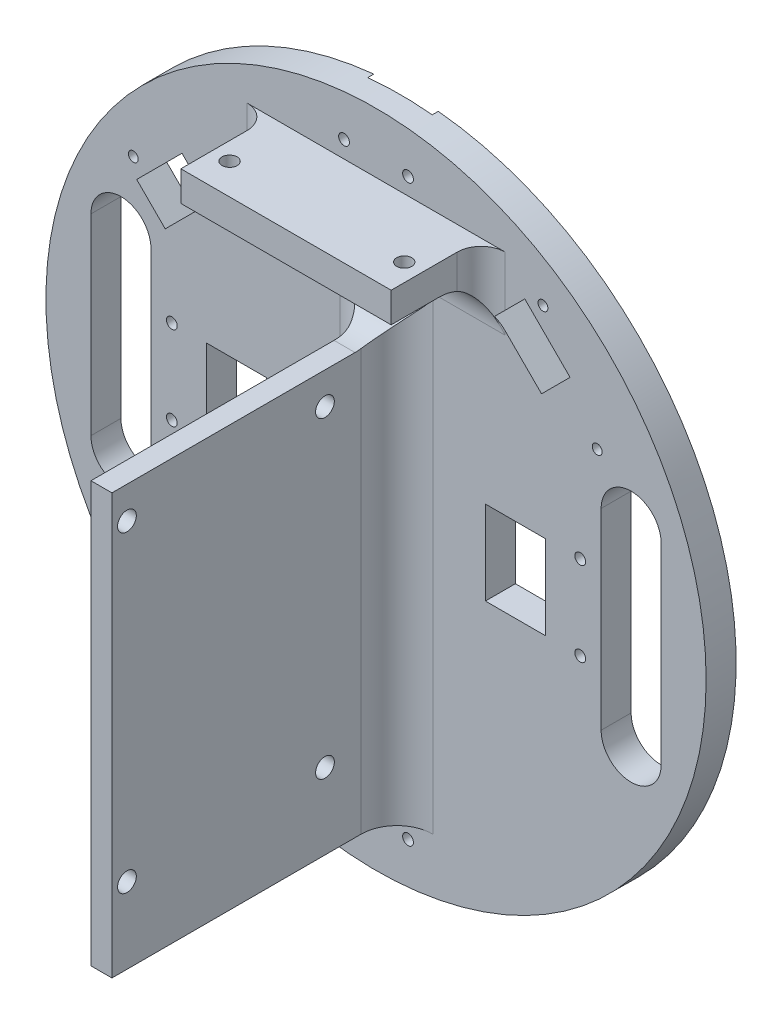
SolidWorks part; units mm, degrees
ref_plane "Front Plane" through (0, 0, 0) normal (0, 0, 1) x (1, 0, 0)
ref_plane "Top Plane" through (0, 0, 0) normal (0, 1, 0) x (1, 0, 0)
ref_plane "Right Plane" through (0, 0, 0) normal (1, 0, 0) x (0, 0, -1)
sketch "Master" plane through (0, 0, 0) normal (0, 0, 1) x (1, 0, 0)
  line L0 (-43.2054, -8.89) -> (-43.2054, 8.89) construction
  line L1 (-46.7961, 27.6322) -> (-27.6322, 46.7961) construction
  line L2 (-69.85, -69.85) -> (69.85, -69.85) construction
  line L3 (-69.85, -69.85) -> (-69.85, 69.85) construction
  line L4 (-69.85, 69.85) -> (69.85, 69.85) construction
  line L5 (69.85, -69.85) -> (69.85, 69.85) construction
  line L6 (-69.85, -69.85) -> (69.85, 69.85) construction
  line L7 (-53.975, 20.32) -> (-53.975, -20.32) construction
  line L8 (-47.625, 20.32) -> (-47.625, -20.32)
  line L9 (-60.325, 20.32) -> (-60.325, -20.32)
  line L10 (0, 69.85) -> (0, -69.85) construction
  line L11 (53.975, 20.32) -> (53.975, -20.32) construction
  line L14 (-18.4785, 50.7873) -> (18.4785, 50.7873) construction
  line L15 (-28.39, -5.09) -> (37.71, -5.09) construction
  line L16 (-28.39, -5.09) -> (-28.39, -46.99) construction
  line L17 (-28.39, -46.99) -> (37.71, -46.99) construction
  line L18 (37.71, -5.09) -> (37.71, -46.99) construction
  line L19 (-14.732, 57.3532) -> (14.732, 57.3532) construction
  line L20 (-14.732, 57.3532) -> (-14.732, 54.5338) construction
  line L21 (-43, 1.27) -> (43, 1.27) construction
  line L22 (-43, 1.27) -> (-43, -53.34) construction
  line L23 (-43, -53.34) -> (43, -53.34) construction
  line L24 (43, 1.27) -> (43, -53.34) construction
  line L25 (-43, 1.27) -> (43, -53.34) construction
  line L26 (-43, -53.34) -> (43, 1.27) construction
  line L27 (-14.732, 44.2468) -> (14.732, 44.2468) construction
  line L28 (14.732, 57.3532) -> (14.732, 54.5338) construction
  line L29 (-14.732, 57.3532) -> (14.732, 44.2468) construction
  line L30 (-14.732, 44.2468) -> (14.732, 57.3532) construction
  line L31 (-18.4785, 54.5338) -> (-14.732, 54.5338) construction
  line L32 (-18.4785, 47.0408) -> (-14.732, 47.0408) construction
  line L33 (14.732, 54.5338) -> (18.4785, 54.5338) construction
  line L34 (14.732, 47.0408) -> (18.4785, 47.0408) construction
  line L35 (-14.732, 47.0408) -> (-14.732, 44.2468) construction
  line L36 (14.732, 47.0408) -> (14.732, 44.2468) construction
  line L37 (-69.85, 69.85) -> (69.85, -69.85) construction
  line L38 (-46.7961, 27.6322) -> (-54.4832, 35.3193) construction
  line L39 (-54.4832, 35.3193) -> (-35.3193, 54.4832) construction
  line L40 (-27.6322, 46.7961) -> (-35.3193, 54.4832) construction
  line L41 (-46.7961, 27.6322) -> (-35.3193, 54.4832) construction
  line L42 (-54.4832, 35.3193) -> (-27.6322, 46.7961) construction
  line L43 (41.0577, 41.0577) -> (31.4758, 50.6397)
  line L44 (41.0577, 41.0577) -> (35.023, 35.023)
  line L45 (31.4758, 50.6397) -> (25.4411, 44.6049)
  line L46 (35.023, 35.023) -> (25.4411, 44.6049)
  line L47 (27.6322, 46.7961) -> (46.7961, 27.6322) construction
  line L48 (27.6322, 46.7961) -> (35.3193, 54.4832) construction
  line L49 (35.3193, 54.4832) -> (54.4832, 35.3193) construction
  line L50 (47.625, 20.32) -> (47.625, -20.32)
  line L51 (-71.8058, -5.08) -> (-14.605, -5.08) construction
  line L52 (-71.8058, -5.08) -> (-71.8058, 5.08) construction
  line L53 (-71.8058, 5.08) -> (-14.605, 5.08) construction
  line L54 (-14.605, -5.08) -> (-14.605, 5.08) construction
  line L55 (-71.8058, -5.08) -> (-14.605, 5.08) construction
  line L56 (-71.8058, 5.08) -> (-14.605, -5.08) construction
  line L57 (60.325, 20.32) -> (60.325, -20.32)
  line L58 (71.8058, 5.08) -> (14.605, 5.08) construction
  line L59 (71.8058, 5.08) -> (14.605, -5.08) construction
  line L60 (14.605, -5.08) -> (14.605, 5.08) construction
  line L61 (71.8058, -5.08) -> (14.605, 5.08) construction
  line L62 (71.8058, -5.08) -> (14.605, -5.08) construction
  line L63 (-41.0577, 41.0577) -> (-50.6397, 31.4758)
  line L64 (-41.0577, 41.0577) -> (-35.023, 35.023)
  line L65 (-50.6397, 31.4758) -> (-44.6049, 25.4411)
  line L66 (-35.023, 35.023) -> (-44.6049, 25.4411)
  line L67 (46.7961, 27.6322) -> (54.4832, 35.3193) construction
  line L68 (27.6322, 46.7961) -> (54.4832, 35.3193) construction
  line L69 (35.3193, 54.4832) -> (46.7961, 27.6322) construction
  line L70 (35.8394, -8.89) -> (23.1394, -8.89)
  line L71 (-35.8394, 8.89) -> (-23.1394, 8.89)
  line L72 (-35.8394, 8.89) -> (-35.8394, -8.89)
  line L73 (-35.8394, -8.89) -> (-23.1394, -8.89)
  line L74 (-23.1394, 8.89) -> (-23.1394, -8.89)
  line L75 (23.1394, 8.89) -> (23.1394, -8.89)
  line L76 (35.8394, 8.89) -> (23.1394, 8.89)
  line L77 (35.8394, 8.89) -> (35.8394, -8.89)
  circle A0 centre (0, 0) radius 69.85
  arc A1 (-47.625, 20.32) -> (-60.325, 20.32) centre (-53.975, 20.32) ccw
  arc A2 (-60.325, -20.32) -> (-47.625, -20.32) centre (-53.975, -20.32) ccw
  circle A3 centre (-43.2054, -8.89) radius 1.143
  circle A4 centre (-43.2054, 8.89) radius 1.143
  arc A7 (47.625, 20.32) -> (60.325, 20.32) centre (53.975, 20.32) cw
  arc A8 (60.325, -20.32) -> (47.625, -20.32) centre (53.975, -20.32) cw
  circle A9 centre (-28.39, -5.09) radius 1.9844 construction
  circle A10 centre (37.71, -5.09) radius 1.9844 construction
  circle A11 centre (37.71, -46.99) radius 1.9844 construction
  circle A12 centre (-28.39, -46.99) radius 1.9844 construction
  arc A13 (-18.4785, 54.5338) -> (-18.4785, 47.0408) centre (-18.4785, 50.7873) ccw construction
  arc A14 (18.4785, 47.0408) -> (18.4785, 54.5338) centre (18.4785, 50.7873) ccw construction
  circle A15 centre (-18.4785, 50.7873) radius 1.6002 construction
  circle A16 centre (18.4785, 50.7873) radius 1.6002 construction
  circle A17 centre (-51.3581, 35.3193) radius 1.0414
  circle A18 centre (-30.7574, 46.7961) radius 1.0414
  circle A19 centre (35.3193, 51.3581) radius 1.0414
  circle A20 centre (46.7961, 30.7574) radius 1.0414
  circle A21 centre (43.2054, -8.89) radius 1.143
  circle A22 centre (43.2054, 8.89) radius 1.143
  point P0 (3.175, -31.115)
  point P3 (-69.85, 0)
  point P4 (69.85, 0)
  point P6 (0, -69.85)
  point P9 (-43.2054, 0)
  point P12 (-53.975, 0)
  point P23 (53.975, 0)
  point P45 (0, -26.035)
  point P48 (0, 50.8)
  point P50 (0, 44.5902)
  point P63 (0, 69.85)
  point P71 (-41.0577, 41.0577)
  point P76 (-49.3914, 49.3914)
  point P77 (-43.2054, 0)
  point P79 (0, -53.34)
  point P85 (41.0577, 41.0577)
  point P91 (49.3914, 49.3914)
  point P109 (0, 0)
  dimension "D1" = 40.64
  dimension "D4" = 2.286
  dimension "D7" = 3.9688
  dimension "D8" = 86
  dimension "D17" = 3.2004
  dimension "D18" = 3.2004
  dimension "D23" = 2.0828
  dimension "D24" = 2.0828
  dimension "D38" = 139.7
  dimension "D2" = 12.7
  dimension "D5" = 66.1
  dimension "D6" = 41.9
  dimension "D9" = 54.61
  dimension "D10" = 14.61
  dimension "D11" = 6.35
  dimension "D12" = 29.464
  dimension "D13" = 36.957
  dimension "D14" = 7.493
  dimension "D15" = 13.1064
  dimension "D16" = 2.8194
  dimension "D19" = 17.78
  dimension "D20" = 19.05
  dimension "D21" = 10.8712
  dimension "D22" = 27.1018
  dimension "D25" = 2.2098
  dimension "D26" = 2.2098
  dimension "D27" = 2.2098
  dimension "D28" = 2.2098
  dimension "D29" = 6.35
  dimension "D31" = 13.97
  dimension "D32" = 9.525
  dimension "D33" = 16.51
  dimension "D34" = 45.72
  dimension "D35" = 10.16
  dimension "D37" = 10.7696
  dimension "D39" = 12.7
  dimension "D36" = 7.366
  dimension "D30" = 2
extrude "Boss-Extrude1" add sketch "Master" along normal blind 6.35 contours A0 A21 A18 A17 A16 A15 A12 A11 A10 A9 A4 A3 A2 L9 A1 L8 L57 A8 L50 A7 A22 region at (0.0831, -0.7021, 0)
sketch "Sketch23" plane through (0, 0, 0) normal (0, 0, 1) x (1, 0, 0)
  line L1 (-22.25, 57.15) -> (22.25, 57.15)
  line L2 (-22.25, 57.15) -> (-22.25, 50.8)
  line L3 (-22.25, 50.8) -> (22.25, 50.8)
  line L4 (22.25, 57.15) -> (22.25, 50.8)
  line L6 (0, 69.85) -> (0, -69.85) construction
  point P4 (0, 57.15)
  dimension "D1" = 44.5
  dimension "D2" = 6.35
  dimension "D3" = 12.7
extrude "Boss-Extrude5" add sketch "Sketch23" along normal blind 25.4
sketch "Sketch11" plane through (0, 0, 0) normal (0, 0, 1) x (1, 0, 0)
  line L0 (6.7691, 60.7441) -> (-6.7691, 60.7441) construction
  line L1 (6.7691, 57.9882) -> (-6.7691, 57.9882)
  line L2 (6.7691, 63.5) -> (-6.7691, 63.5)
  line L3 (0, 0) -> (-27.6628, 0) construction
  line L4 (0, 69.85) -> (0, -69.85) construction
  line L5 (6.7691, -60.7441) -> (-6.7691, -60.7441) construction
  line L6 (6.7691, -57.9882) -> (-6.7691, -57.9882)
  line L7 (6.7691, -63.5) -> (-6.7691, -63.5)
  arc A0 (6.7691, 57.9882) -> (6.7691, 63.5) centre (6.7691, 60.7441) ccw
  arc A1 (-6.7691, 63.5) -> (-6.7691, 57.9882) centre (-6.7691, 60.7441) ccw
  circle A2 centre (-6.7691, 60.7441) radius 1.143
  circle A3 centre (6.7691, 60.7441) radius 1.143
  arc A4 (6.7691, -57.9882) -> (6.7691, -63.5) centre (6.7691, -60.7441) cw
  arc A5 (-6.7691, -63.5) -> (-6.7691, -57.9882) centre (-6.7691, -60.7441) cw
  circle A6 centre (6.7691, -60.7441) radius 1.143
  circle A7 centre (-6.7691, -60.7441) radius 1.143
  circle A8 centre (0, 60.7441) radius 11.1125
  circle A9 centre (0, -60.7441) radius 11.1125
  point P2 (0, 60.7441)
  point P7 (-9.525, 60.7441)
  point P8 (9.525, 60.7441)
  point P21 (0, -60.7441)
  point P30 (9.525, -60.7441)
  point P31 (-9.525, -60.7441)
  dimension "D3" = 2.286
  dimension "D5" = 22.225
  dimension "D1" = 19.05
  dimension "D2" = 13.5382
  dimension "D4" = 6.35
extrude "Cut-Extrude4" cut sketch "Sketch11" along normal blind 1.27 contours A8 | A9
sketch "Sketch14" plane through (0, 0, 0) normal (0, 0, 1) x (1, 0, 0)
  line L0 (6.7691, 60.7441) -> (-6.7691, 60.7441) construction
  line L1 (6.7691, 57.9882) -> (-6.7691, 57.9882)
  line L2 (6.7691, 63.5) -> (-6.7691, 63.5)
  line L3 (0, 0) -> (-27.6628, 0) construction
  line L4 (0, 69.85) -> (0, -69.85) construction
  line L5 (6.7691, -60.7441) -> (-6.7691, -60.7441) construction
  line L6 (6.7691, -57.9882) -> (-6.7691, -57.9882)
  line L7 (6.7691, -63.5) -> (-6.7691, -63.5)
  arc A0 (6.7691, 57.9882) -> (6.7691, 63.5) centre (6.7691, 60.7441) ccw
  arc A1 (-6.7691, 63.5) -> (-6.7691, 57.9882) centre (-6.7691, 60.7441) ccw
  circle A2 centre (-6.7691, 60.7441) radius 1.143
  circle A3 centre (6.7691, 60.7441) radius 1.143
  arc A4 (6.7691, -57.9882) -> (6.7691, -63.5) centre (6.7691, -60.7441) cw
  arc A5 (-6.7691, -63.5) -> (-6.7691, -57.9882) centre (-6.7691, -60.7441) cw
  circle A6 centre (6.7691, -60.7441) radius 1.143
  circle A7 centre (-6.7691, -60.7441) radius 1.143
  arc A9 (-6.8221, 69.5161) -> (6.8221, 69.5161) centre (0, 60.7441) ccw construction
  arc A10 (6.8221, -69.5161) -> (-6.8221, -69.5161) centre (0, -60.7441) ccw construction
  point P2 (0, 60.7441)
  point P7 (-9.525, 60.7441)
  point P8 (9.525, 60.7441)
  point P21 (0, -60.7441)
  point P30 (9.525, -60.7441)
  point P31 (-9.525, -60.7441)
  dimension "D3" = 2.286
  dimension "D1" = 19.05
  dimension "D2" = 13.5382
extrude "Cut-Extrude6" cut sketch "Sketch14" along normal through all contours A2 | A3 | A6 | A7
sketch "Sketch21" plane through (0, 0, 6.35) normal (0, 0, 1) x (1, 0, 0)
  line L1 (0, 31.75) -> (4.445, 31.75)
  line L2 (0, 31.75) -> (0, -57.15)
  line L3 (0, -57.15) -> (4.445, -57.15)
  line L4 (4.445, 31.75) -> (4.445, -57.15)
  line L5 (0, 69.85) -> (0, -69.85) construction
  dimension "D1" = 4.445
  dimension "D2" = 88.9
  dimension "D3" = 12.7
extrude "Boss-Extrude4" add sketch "Sketch21" along normal blind 60.325
sketch "Sketch22" plane through (0, 0, 0) normal (-1, 0, 0) x (0, 0, 1)
  line L0 (21.6, -41.09) -> (21.6, 25.01) construction
  line L1 (21.6, -41.09) -> (63.5, -41.09) construction
  line L2 (63.5, -41.09) -> (63.5, 25.01) construction
  line L3 (21.6, 25.01) -> (63.5, 25.01) construction
  line L4 (15.24, -55.7) -> (15.24, 30.3) construction
  line L5 (15.24, -55.7) -> (69.85, -55.7) construction
  line L6 (69.85, -55.7) -> (69.85, 30.3) construction
  line L7 (15.24, 30.3) -> (69.85, 30.3) construction
  line L8 (15.24, -55.7) -> (69.85, 30.3) construction
  line L9 (69.85, -55.7) -> (15.24, 30.3) construction
  line L10 (6.35, -69.85) -> (6.35, 69.85) construction
  line L11 (66.675, 31.75) -> (6.35, 31.75) construction
  line L12 (15.24, 30.3) -> (15.24, 31.75) construction
  line L15 (15.24, -55.7) -> (15.24, -57.15) construction
  line L18 (66.675, -57.15) -> (6.35, -57.15) construction
  circle A0 centre (21.6, -41.09) radius 1.9844
  circle A1 centre (21.6, 25.01) radius 1.9844
  circle A2 centre (63.5, 25.01) radius 1.9844
  circle A3 centre (63.5, -41.09) radius 1.9844
  point P12 (69.85, -12.7)
  point P13 (42.545, -12.7)
  dimension "D2" = 3.9688
  dimension "D1" = 41.9
  dimension "D3" = 54.61
  dimension "D4" = 14.61
  dimension "D5" = 6.35
  dimension "D6" = 86
  dimension "D7" = 66.1
  dimension "D8" = 8.89
extrude "Cut-Extrude8" cut sketch "Sketch22" against normal blind 60.325
sketch "Sketch24" plane through (0, 57.15, 0) normal (0, 1, 0) x (1, 0, 0)
  line L0 (22.25, -25.4) -> (-22.25, -25.4) construction
  line L2 (-18.4785, -18.8595) -> (18.4785, -18.8595) construction
  line L3 (-14.732, -12.2936) -> (14.732, -12.2936) construction
  line L4 (-14.732, -12.2936) -> (-14.732, -15.113) construction
  line L5 (-14.732, -25.4) -> (14.732, -25.4) construction
  line L6 (14.732, -12.2936) -> (14.732, -15.113) construction
  line L7 (-14.732, -12.2936) -> (14.732, -25.4) construction
  line L8 (-14.732, -25.4) -> (14.732, -12.2936) construction
  line L9 (-18.4785, -15.113) -> (-14.732, -15.113) construction
  line L10 (-18.4785, -22.606) -> (-14.732, -22.606) construction
  line L11 (14.732, -15.113) -> (18.4785, -15.113) construction
  line L12 (14.732, -22.606) -> (18.4785, -22.606) construction
  line L13 (-14.732, -22.606) -> (-14.732, -25.4) construction
  line L14 (14.732, -22.606) -> (14.732, -25.4) construction
  arc A0 (-18.4785, -15.113) -> (-18.4785, -22.606) centre (-18.4785, -18.8595) ccw construction
  arc A1 (18.4785, -22.606) -> (18.4785, -15.113) centre (18.4785, -18.8595) ccw construction
  circle A2 centre (-18.4785, -18.8595) radius 1.6002
  circle A3 centre (18.4785, -18.8595) radius 1.6002
  point P3 (0, -25.4)
  point P7 (0, -18.8468)
  point P21 (0.2328, 1.7216)
  dimension "D6" = 3.2004
  dimension "D7" = 3.2004
  dimension "D1" = 29.464
  dimension "D2" = 36.957
  dimension "D3" = 7.493
  dimension "D4" = 13.1064
  dimension "D5" = 2.8194
extrude "Cut-Extrude9" cut sketch "Sketch24" against normal blind 25.4
fillet "Fillet6" radius 7.62 2 edges at (0, -12.7, 6.35) (4.445, -12.7, 6.35)
fillet "Fillet11" radius 8.89 2 edges at (2.2225, 31.75, 6.35) (0, 50.8, 6.35)
fillet "Fillet13" radius 5.08 2 edges at (-22.25, 49.53, 6.35) (22.25, 49.53, 6.35)
